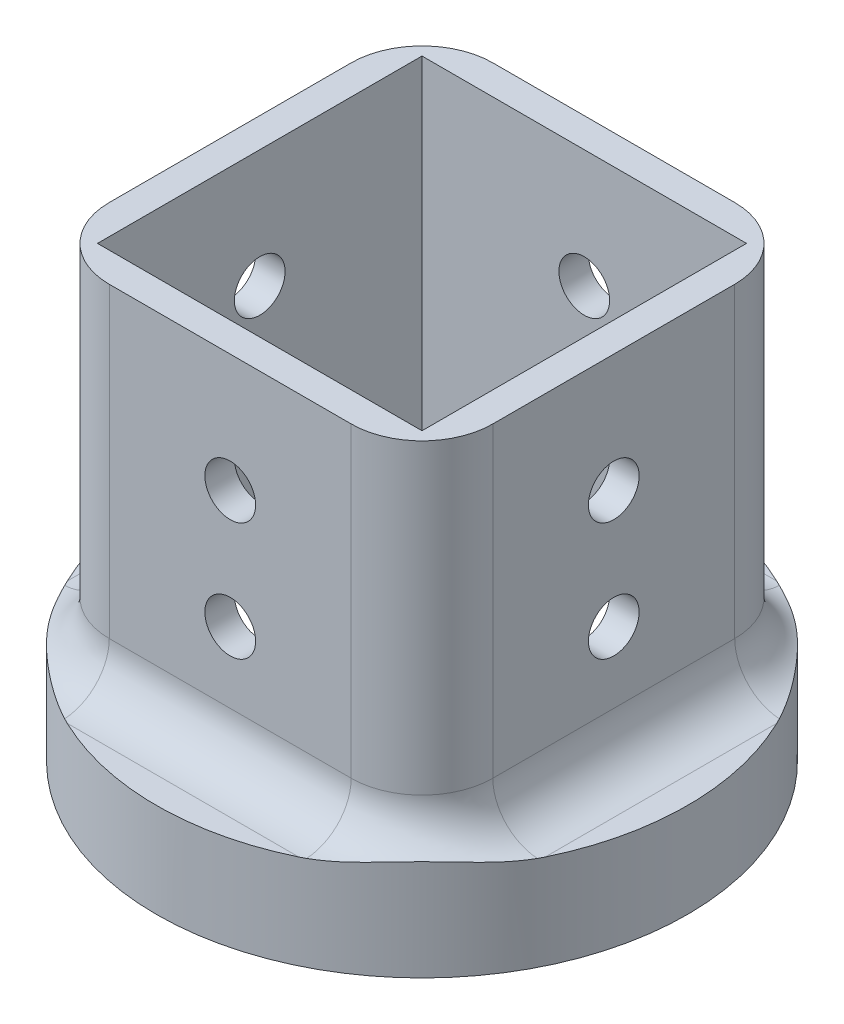
SolidWorks part; units mm, degrees
ref_plane "前视基准面" through (0, 0, 0) normal (0, 0, 1) x (1, 0, 0)
ref_plane "上视基准面" through (0, 0, 0) normal (0, 1, 0) x (1, 0, 0)
ref_plane "右视基准面" through (0, 0, 0) normal (1, 0, 0) x (0, 0, -1)
other "Configuration Table"
sketch "草图1" plane through (0, 0, 0) normal (0, 1, 0) x (1, 0, 0)
  circle A0 centre (0, 0) radius 20.5
  circle A1 centre (0, 0) radius 22.5
  dimension "D1" = 41
  dimension "D2" = 2
extrude "凸台-拉伸1" add sketch "草图1" along normal blind 6
sketch "草图2" plane through (0, 6, 0) normal (0, 1, 0) x (1, 0, 0)
  circle A0 centre (0, 0) radius 22.5
extrude "凸台-拉伸2" add sketch "草图2" along normal blind 2
sketch "草图3" plane through (0, 8, 0) normal (0, 1, 0) x (1, 0, 0)
  line L0 (-13.25, 13.25) -> (13.25, 13.25)
  line L1 (-10.25, -10.25) -> (10.25, -10.25)
  line L2 (-10.25, -10.25) -> (-10.25, 10.25)
  line L3 (-10.25, 10.25) -> (10.25, 10.25)
  line L4 (10.25, -10.25) -> (10.25, 10.25)
  line L5 (-10.25, -10.25) -> (10.25, 10.25) construction
  line L6 (-10.25, 10.25) -> (10.25, -10.25) construction
  line L7 (13.25, -13.25) -> (13.25, 13.25)
  line L8 (-13.25, -13.25) -> (13.25, -13.25)
  line L9 (-13.25, -13.25) -> (-13.25, 13.25)
  point P0 (0, 0)
  dimension "D1" = 20.5
  dimension "D2" = 20.5
  dimension "D3" = 3
extrude "凸台-拉伸3" add sketch "草图3" along normal blind 30
sketch "草图4" plane through (0, 0, 13.25) normal (0, 0, 1) x (1, 0, 0)
  line L0 (0, 38) -> (0, 28)
  line L1 (-13.25, 38) -> (13.25, 38) construction
  line L2 (0, 28) -> (0, 18)
  circle A0 centre (0, 28) radius 2.15
  circle A1 centre (0, 18) radius 2.15
  dimension "D2" = 4.3
  dimension "D4" = 4.3
  dimension "D1" = 10
  dimension "D3" = 10
extrude "切除-拉伸1" cut sketch "草图4" against normal blind 30
sketch "草图5" plane through (13.25, 0, 0) normal (1, 0, 0) x (0, 0, -1)
  line L0 (0, 38) -> (0, 28)
  line L1 (-13.25, 38) -> (13.25, 38) construction
  line L2 (0, 28) -> (0, 18)
  circle A0 centre (0, 28) radius 2.15
  circle A1 centre (0, 18) radius 2.15
  dimension "D2" = 4.3
  dimension "D4" = 4.3
  dimension "D1" = 10
  dimension "D3" = 10
extrude "切除-拉伸2" cut sketch "草图5" against normal blind 30
fillet "圆角1" radius 3 4 edges at (-13.25, 23, 13.25) (13.25, 23, -13.25) (13.25, 23, 13.25) (-13.25, 23, -13.25)
sketch "草图7" plane through (0, 38, 0) normal (0, 1, 0) x (1, 0, 0)
  line L5 (-13.25, -13.25) -> (13.25, -13.25)
  line L6 (-13.25, -13.25) -> (-13.25, 13.25)
  line L7 (-13.25, 13.25) -> (13.25, 13.25)
  line L8 (-16.25, 10.25) -> (-16.25, -10.25)
  line L9 (-10.25, -16.25) -> (10.25, -16.25)
  line L10 (16.25, -10.25) -> (16.25, 10.25)
  line L11 (10.25, 16.25) -> (-10.25, 16.25)
  line L12 (-16.25, 10.25) -> (-16.25, -10.25)
  line L13 (-10.25, -16.25) -> (10.25, -16.25)
  line L14 (16.25, -10.25) -> (16.25, 10.25)
  line L15 (10.25, 16.25) -> (-10.25, 16.25)
  line L16 (13.25, -13.25) -> (13.25, 13.25)
  line L17 (-13.25, -13.25) -> (13.25, 13.25) construction
  line L18 (-13.25, 13.25) -> (13.25, -13.25) construction
  arc A8 (-16.25, -10.25) -> (-10.25, -16.25) centre (-10.25, -10.25) ccw
  arc A9 (10.25, -16.25) -> (16.25, -10.25) centre (10.25, -10.25) ccw
  arc A10 (16.25, 10.25) -> (10.25, 16.25) centre (10.25, 10.25) ccw
  arc A11 (-10.25, 16.25) -> (-16.25, 10.25) centre (-10.25, 10.25) ccw
  arc A12 (-16.25, -10.25) -> (-10.25, -16.25) centre (-10.25, -10.25) ccw
  arc A13 (10.25, -16.25) -> (16.25, -10.25) centre (10.25, -10.25) ccw
  arc A14 (16.25, 10.25) -> (10.25, 16.25) centre (10.25, 10.25) ccw
  arc A15 (-10.25, 16.25) -> (-16.25, 10.25) centre (-10.25, 10.25) ccw
  point P0 (0, 0)
  dimension "D1" = 3
extrude "凸台-拉伸4" add sketch "草图7" against normal blind 30
sketch "草图8" plane through (0, 38, 0) normal (0, 1, 0) x (1, 0, 0)
  line L0 (-13.75, 13.75) -> (13.75, 13.75)
  line L1 (-13.25, -13.25) -> (13.25, -13.25)
  line L2 (-13.25, -13.25) -> (-13.25, 13.25)
  line L4 (13.25, -13.25) -> (13.25, 13.25)
  line L5 (-13.25, -13.25) -> (13.25, 13.25) construction
  line L6 (-13.25, 13.25) -> (13.25, -13.25) construction
  line L7 (13.75, -13.75) -> (13.75, 13.75)
  line L8 (-13.75, -13.75) -> (13.75, -13.75)
  line L9 (-13.75, -13.75) -> (-13.75, 13.75)
  line L10 (-13.25, 13.25) -> (13.25, 13.25) construction
  point P0 (0, 0)
  dimension "D1" = 0.5
extrude "切除-拉伸4" cut sketch "草图8" against normal through all
fillet "圆角2" radius 4 8 edges at (-14.4926, 8, -14.4926) (0, 8, -16.25) (14.4926, 8, -14.4926) (16.25, 8, 0) (14.4926, 8, 14.4926) (0, 8, 16.25) (-14.4926, 8, 14.4926) (-16.25, 8, 0)
sketch "草图9" plane through (16.25, 0, 0) normal (1, 0, 0) x (0, 0, -1)
  line L0 (0, 38) -> (0, 28)
  line L1 (-10.25, 38) -> (10.25, 38) construction
  line L2 (0, 28) -> (0, 18)
  circle A0 centre (0, 28) radius 2.15
  circle A1 centre (0, 18) radius 2.15
  dimension "D2" = 4.3
  dimension "D4" = 4.3
  dimension "D1" = 10
  dimension "D3" = 10
extrude "切除-拉伸5" cut sketch "草图9" against normal through all
sketch "草图10" plane through (0, 0, 16.25) normal (0, 0, 1) x (1, 0, 0)
  line L0 (0, 38) -> (0, 28)
  line L1 (-10.25, 38) -> (10.25, 38) construction
  line L2 (0, 28) -> (0, 18)
  circle A0 centre (0, 28) radius 2.15
  circle A1 centre (0, 18) radius 2.15
  dimension "D2" = 4.3
  dimension "D4" = 4.3
  dimension "D1" = 10
  dimension "D3" = 10
extrude "切除-拉伸6" cut sketch "草图10" against normal through all
